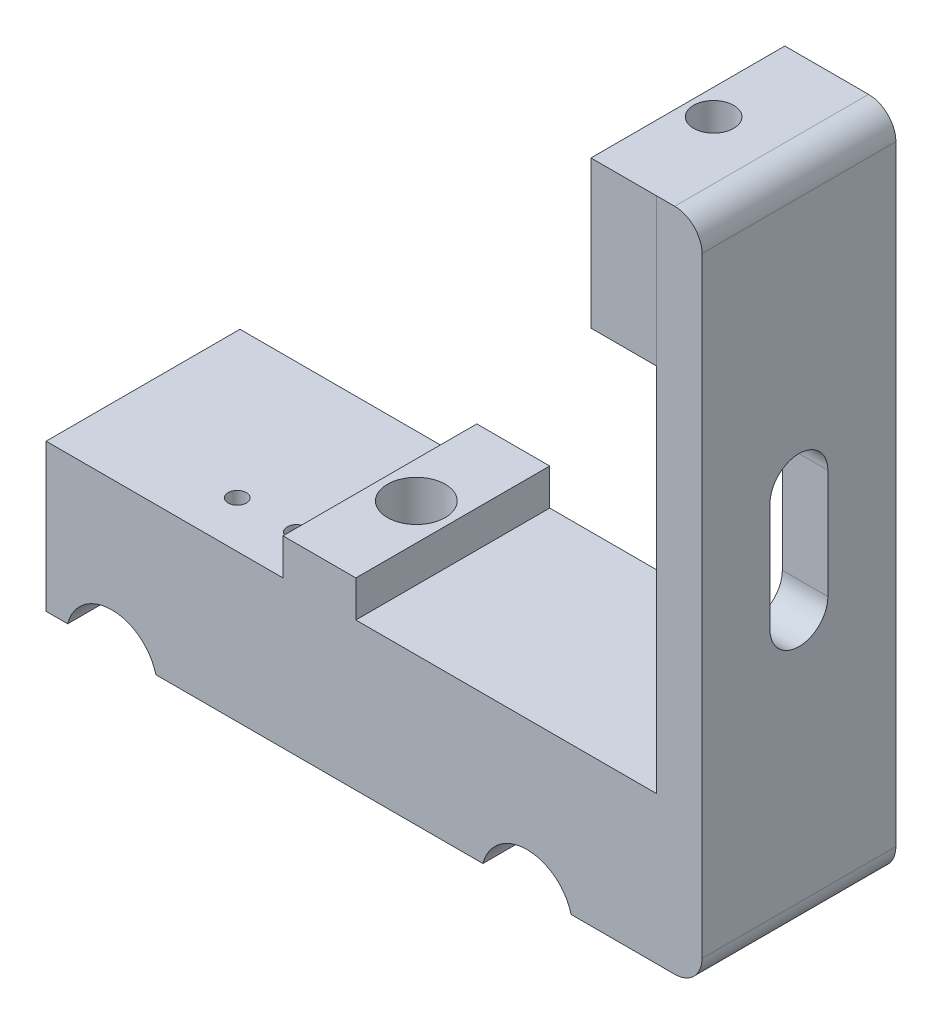
SolidWorks part; units mm, degrees
ref_plane "Front Plane" through (0, 0, 0) normal (0, 0, 1) x (1, 0, 0)
ref_plane "Top Plane" through (0, 0, 0) normal (0, 1, 0) x (1, 0, 0)
ref_plane "Right Plane" through (0, 0, 0) normal (1, 0, 0) x (0, 0, -1)
sketch "Sketch2" plane through (0, 0, 0) normal (0, 0, 1) x (1, 0, 0)
  line L0 (10.1, 0) -> (-10.1, 0)
  line L1 (-10.1, 0) -> (-10.1, 1.7099)
  line L2 (-10.1, 1.7099) -> (-6.2548, 7)
  line L3 (-6.2548, 7) -> (6.2548, 7)
  line L4 (0, 7) -> (0, 0)
  line L5 (0, 0) -> (0, 9.2516) construction
  line L6 (10.1, 1.7099) -> (6.2548, 7)
  line L7 (10.1, 0) -> (10.1, 1.7099)
  dimension "D1" = 20.2
  dimension "D2" = 7
extrude "Boss-Extrude1" add sketch "Sketch2" along normal blind 10.8 contours L4 L3 L2 L1 L0 | L0 L7 L6 L3 L4 region at (4.4168, 3.2082, 0) region at (-4.4168, 3.2082, 0)
sketch "Sketch4" plane through (0, 0, 0) normal (0, 0, 1) x (1, 0, 0)
  line L0 (-4, 0) -> (-4, -4.8)
  line L1 (10.1, 0) -> (-10.1, 0) construction
  line L2 (-4, -4.8) -> (-30, -4.8)
  line L3 (-30, -4.8) -> (-30, -29.8)
  line L4 (-30, -29.8) -> (30, -29.8)
  line L5 (0, 0) -> (0, -29.8) construction
  line L6 (0, -29.8) -> (0, 0)
  line L7 (4, 0) -> (-4, 0)
  line L8 (0, 0) -> (0, -30.5381) construction
  line L9 (30, -4.8) -> (30, -29.8)
  line L10 (4, -4.8) -> (30, -4.8)
  line L11 (4, 0) -> (4, -4.8)
  line L13 (-30, -20.98) -> (30, -20.98)
  line L14 (-30, -20.98) -> (-30, -23.48)
  line L15 (-30, -23.48) -> (30, -23.48)
  line L16 (30, -20.98) -> (30, -23.48)
  dimension "D1" = 4.8
  dimension "D2" = 4
  dimension "D3" = 25
  dimension "D4" = 60
  dimension "D6" = 8.82
extrude "Boss-Extrude2" add sketch "Sketch4" along normal mid plane 21.28 contours L6 L7 L0 L2 L3 L4 | L11 L7 L6 L4 L9 L10 region at (-14.5054, -12.4909, 0) region at (14.5054, -12.4909, 0)
sketch "Sketch5" plane through (0, 0, 0) normal (0, 0, 1) x (1, 0, 0)
  line L0 (-29.791, -22.2274) -> (26.9734, -22.2274) construction
  line L3 (0, -20.98) -> (0, 7) construction
  line L5 (-6.2548, 7) -> (6.2548, 7) construction
  line L20 (-30, -20.98) -> (30, -20.98) construction
  circle A0 centre (-22.791, -22.2274) radius 5
  circle A1 centre (22.791, -22.2274) radius 5
  dimension "D1" = 7
extrude "Cut-Extrude1" cut sketch "Sketch5" along normal through all both and the other way through all
fillet "Fillet1" radius 1 6 edges at (-10.1, 0, 5.4) (-10.1, 1.7099, 5.4) (-6.2548, 7, 5.4) (6.2548, 7, 5.4) (10.1, 0, 5.4) (10.1, 1.7099, 5.4)
sketch "Sketch6" plane through (30, 0, 0) normal (1, 0, 0) x (0, 0, -1)
  line L0 (-10.64, -20.98) -> (10.64, -20.98) construction
  line L1 (-10.64, -4.8) -> (10.64, -4.8)
  line L2 (-10.64, -4.8) -> (-10.64, -20.98)
  line L3 (-10.64, -20.98) -> (10.64, -20.98)
  line L4 (10.64, -4.8) -> (10.64, -20.98)
extrude "Boss-Extrude3" add sketch "Sketch6" along normal blind 12
sketch "Sketch7" plane through (0, -4.8, 0) normal (0, 1, 0) x (1, 0, 0)
  line L0 (4, -10.64) -> (42, -10.64) construction
  line L1 (42, 10.6413) -> (37, 10.6413)
  line L2 (42, 10.6413) -> (42, -10.64)
  line L3 (42, -10.64) -> (37, -10.64)
  line L4 (37, 10.6413) -> (37, -10.64)
  dimension "D1" = 5
extrude "Boss-Extrude4" add sketch "Sketch7" along normal blind 56.83
sketch "Sketch8" plane through (37, 0, 0) normal (-1, 0, 0) x (0, 0, 1)
  line L0 (-10.6413, 52.03) -> (-10.6413, -4.8) construction
  line L1 (10.643, 52.03) -> (-10.6413, 52.03)
  line L2 (10.643, 52.03) -> (10.643, 35.85)
  line L3 (10.643, 35.85) -> (-10.6413, 35.85)
  line L4 (-10.6413, 52.03) -> (-10.6413, 35.85)
  dimension "D1" = 16.18
extrude "Boss-Extrude5" add sketch "Sketch8" along normal blind 7.19
fillet "Fillet3" radius 3 2 edges at (42, 52.03, -0.0007) (42, -20.98, 0)
sketch "Sketch9" plane through (0, -20.98, 0) normal (0, -1, 0) x (1, 0, 0)
  line L0 (27.6329, 0) -> (27.6329, 10.8) construction
  line L2 (27.6329, 10.64) -> (39, 10.64) construction
  circle A0 centre (32.6329, 0) radius 2.2
  dimension "D1" = 5
  dimension "D2" = 10.64
extrude "Cut-Extrude2" cut sketch "Sketch9" against normal through all
sketch "Sketch10" plane through (0, -20.98, 0) normal (0, -1, 0) x (1, 0, 0)
  line L2 (-17.9491, 0) -> (-17.9491, 10.8) construction
  line L3 (-17.9491, 10.64) -> (17.9491, 10.64) construction
  circle A0 centre (0.0009, 0) radius 3.175
  dimension "D1" = 10.64
  dimension "D2" = 17.95
extrude "Cut-Extrude3" cut sketch "Sketch10" against normal through all
sketch "Sketch11" plane through (0, 0, 10.8) normal (0, 0, 1) x (1, 0, 0)
  line L0 (9.1, 0) -> (-9.1, 0) construction
  line L1 (-12.6098, 8.9215) -> (12.3675, 8.9215)
  line L2 (-12.6098, 8.9215) -> (-12.6098, -0.8)
  line L3 (-12.6098, -0.8) -> (12.3675, -0.8)
  line L4 (12.3675, 8.9215) -> (12.3675, -0.8)
  dimension "D1" = 0.8
extrude "Cut-Extrude4" cut sketch "Sketch11" against normal through all
sketch "Sketch12" plane through (0, -20.98, 0) normal (0, -1, 0) x (1, 0, 0)
  arc A0 (-8.6262, 5.538) -> (-6.6262, 5.538) centre (-7.6262, 5.538) ccw construction
  arc A1 (-6.6262, 5.538) -> (-8.6262, 5.538) centre (-7.6262, 5.538) ccw construction
  arc A2 (-15.1262, 5.538) -> (-13.1262, 5.538) centre (-14.1262, 5.538) ccw construction
  arc A3 (-13.1262, 5.538) -> (-15.1262, 5.538) centre (-14.1262, 5.538) ccw construction
  arc A4 (-8.6262, 5.538) -> (-6.6262, 5.538) centre (-7.6262, 5.538) ccw
  arc A5 (-6.6262, 5.538) -> (-8.6262, 5.538) centre (-7.6262, 5.538) ccw
  arc A6 (-15.1262, 5.538) -> (-13.1262, 5.538) centre (-14.1262, 5.538) ccw
  arc A7 (-13.1262, 5.538) -> (-15.1262, 5.538) centre (-14.1262, 5.538) ccw
extrude "Cut-Extrude5" cut sketch "Sketch12" against normal up to next
sketch "Sketch13" plane through (42, 0, 0) normal (1, 0, 0) x (0, 0, -1)
  line L0 (10.6413, 49.03) -> (-10.64, 49.03) construction
  line L1 (3.175, 21.525) -> (3.175, 9.525)
  line L2 (-3.175, 21.525) -> (-3.175, 9.525)
  arc A0 (3.175, 21.525) -> (-3.175, 21.525) centre (0, 21.525) ccw
  arc A1 (-3.175, 9.525) -> (3.175, 9.525) centre (0, 9.525) ccw
  dimension "D1" = 27.505
  dimension "D2" = 12
extrude "Cut-Extrude6" cut sketch "Sketch13" against normal through all
